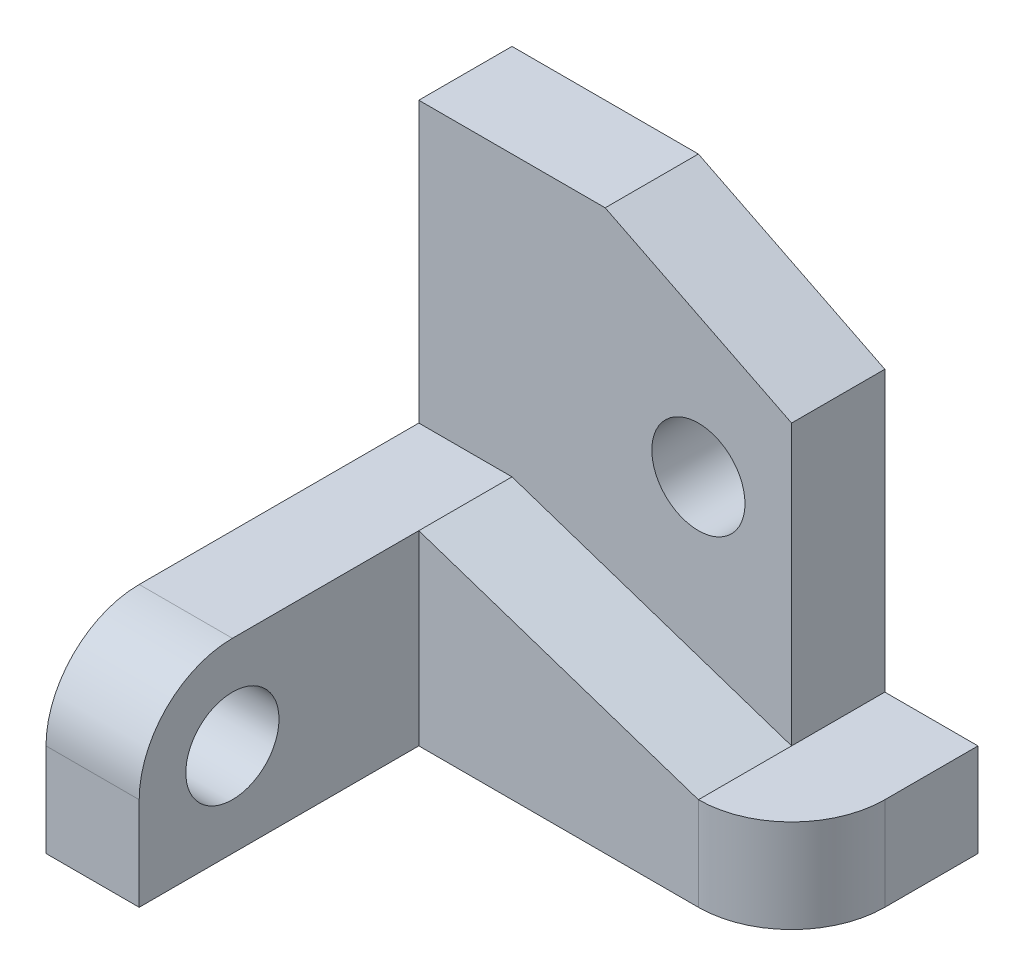
SolidWorks part; units mm, degrees
ref_plane "前基準面" through (0, 0, 0) normal (0, 0, 1) x (1, 0, 0)
ref_plane "上基準面" through (0, 0, 0) normal (0, 1, 0) x (1, 0, 0)
ref_plane "右基準面" through (0, 0, 0) normal (1, 0, 0) x (0, 0, -1)
sketch "草圖1" plane through (0, 0, 0) normal (0, 1, 0) x (1, 0, 0)
  line L0 (20, 5) -> (20, 0)
  line L1 (0, 0) -> (20, 0)
  line L2 (0, 0) -> (0, 10)
  line L3 (0, 10) -> (25, 10)
  line L4 (25, 5) -> (25, 10)
  line L5 (20, 10) -> (0, 10)
  line L6 (20, 10) -> (20, 5)
  line L7 (20, 5) -> (0, 5)
  line L8 (0, 10) -> (0, 5)
  arc A0 (20, 0) -> (25, 5) centre (20, 5) ccw
  dimension "D5" = 5
  dimension "D1" = 10
  dimension "D2" = 25
  dimension "D3" = 5
  dimension "D4" = 5
extrude "填料-伸長1" add sketch "草圖1" along normal blind 5 contours L0 A0 L4 L3 L6 region at (22.3337, 0, -5.4667)
extrude "填料-伸長2" add sketch "草圖1<3>" along normal blind 10 contours L0 L7 L2 L1 region at (10, 0, -2.5)
sketch "草圖1<3>" plane through (0, 0, 0) normal (0, 1, 0) x (1, 0, 0) same geometry as "草圖1"
extrude "填料-伸長3" add sketch "草圖1<4>" along normal blind 25 contours L7 L6 L3 L2 region at (10, 0, -7.5)
sketch "草圖1<4>" plane through (0, 0, 0) normal (0, 1, 0) x (1, 0, 0) same geometry as "草圖1"
sketch "草圖2" plane through (0, 0, -5) normal (0, 0, 1) x (1, 0, 0)
  line L0 (20, 25) -> (0, 25) construction
  line L1 (10, 25) -> (20, 20)
  line L3 (20, 20) -> (20, 25)
  line L4 (20, 25) -> (10, 25)
  line L5 (20, 25) -> (20, 10) construction
  circle A0 centre (15, 15) radius 2.5
  dimension "D5" = 5
  dimension "D1" = 10
  dimension "D2" = 5
  dimension "D3" = 5
  dimension "D4" = 10
extrude "除料-伸長1" cut sketch "草圖2" against normal blind 25
sketch "草圖3" plane through (0, 0, 0) normal (0, 0, 1) x (1, 0, 0)
  line L0 (20, 5) -> (5, 10)
  line L1 (0, 10) -> (20, 10) construction
  line L2 (5, 10) -> (20, 10)
  line L3 (20, 10) -> (20, 5)
  dimension "D1" = 15
extrude "除料-伸長2" cut sketch "草圖3" against normal up to surface (5 mm away) up to face at (10, 18, -5)
sketch "草圖4" plane through (0, 0, 0) normal (1, 0, 0) x (0, 0, -1)
  line L0 (0, 10) -> (-10, 10)
  line L1 (-15, 5) -> (-15, 0)
  line L2 (-15, 0) -> (0, 0)
  line L3 (0, 10) -> (0, 5) construction
  line L4 (0, 10) -> (0, 0)
  arc A0 (-10, 10) -> (-15, 5) centre (-10, 5) ccw
  circle A1 centre (-10, 5) radius 2.5
  dimension "D2" = 5
  dimension "D3" = 5
  dimension "D1" = 15
extrude "填料-伸長4" add sketch "草圖4" along normal blind 5
scale "縮放比例1" scale about centroid uniform scaling yes scale factor 0.2
